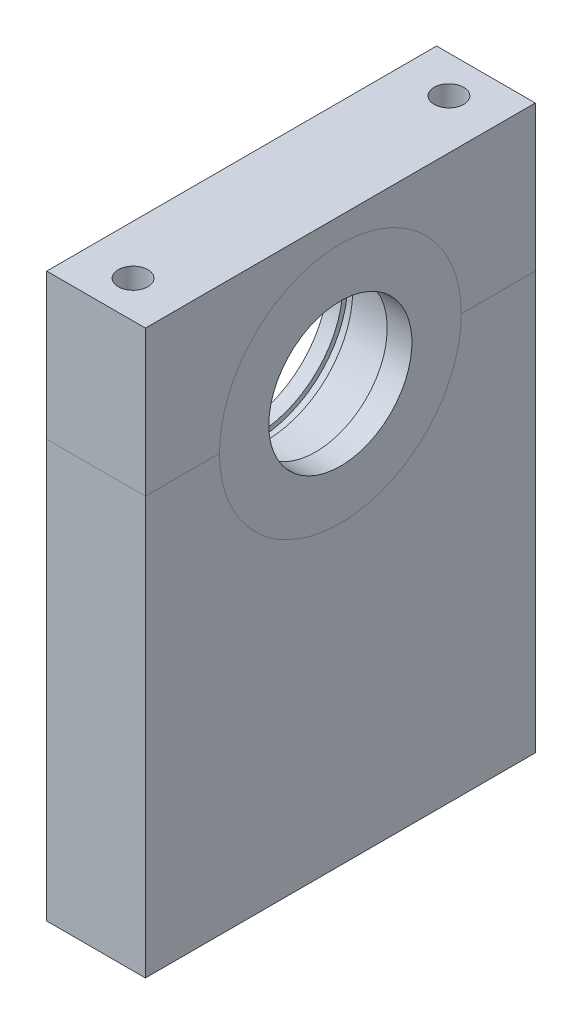
SolidWorks part; units mm, degrees
ref_plane "Front Plane" through (0, 0, 0) normal (0, 0, 1) x (1, 0, 0)
ref_plane "Top Plane" through (0, 0, 0) normal (0, 1, 0) x (1, 0, 0)
ref_plane "Right Plane" through (0, 0, 0) normal (1, 0, 0) x (0, 0, -1)
sketch "Sketch1" plane through (0, 0, 0) normal (0, 0, 1) x (1, 0, 0)
  line L0 (-44.079, 28.0482) -> (-34.079, 28.0482)
  line L1 (-34.079, 28.0482) -> (-34.079, 25.0482)
  line L2 (-34.079, 25.0482) -> (-29.079, 25.0482)
  line L3 (-29.079, 25.0482) -> (-29.079, 35.0482)
  line L4 (-29.079, 35.0482) -> (-49.079, 35.0482)
  line L5 (-49.079, 35.0482) -> (-49.079, 28.0482)
  line L6 (-49.079, 28.0482) -> (-46.079, 28.0482)
  line L7 (-46.079, 28.0482) -> (-46.079, 29.0482)
  line L8 (-46.079, 29.0482) -> (-44.079, 29.0482)
  line L9 (-44.079, 29.0482) -> (-44.079, 28.0482)
  line L10 (-85.0679, 10.5482) -> (6.0387, 10.5482) construction
  dimension "D1" = 24.5
  dimension "D2" = 20
  dimension "D3" = 17.5
  dimension "D4" = 2
  dimension "D5" = 10
  dimension "D6" = 3
  dimension "D7" = 1
  dimension "D8" = 3
revolve "Revolve1" add sketch "Sketch1" angle 360 about L10
sketch "Sketch2" plane through (-49.079, 0, 0) normal (-1, 0, 0) x (0, 0, 1)
  line L0 (-24.5, 10.5482) -> (-39.5, 10.5482)
  line L1 (-39.5, -18.9518) -> (39.5, -18.9518)
  line L2 (-39.5, -18.9518) -> (-39.5, 40.0482)
  line L3 (-39.5, 40.0482) -> (39.5, 40.0482)
  line L4 (39.5, -18.9518) -> (39.5, 40.0482)
  line L5 (0, 40.0482) -> (0, -18.9518) construction
  line L6 (-39.5, 10.5482) -> (39.5, 10.5482) construction
  line L7 (24.5, 10.5482) -> (39.5, 10.5482)
  line L8 (-34.5, 40.0482) -> (-34.5, -18.9518) construction
  line L9 (-29.5, 40.0482) -> (-29.5, -18.9518) construction
  line L10 (29.5, 40.0482) -> (29.5, -18.9518) construction
  line L11 (34.5, 40.0482) -> (34.5, -18.9518) construction
  circle A0 centre (0, 10.5482) radius 24.5 construction
  circle A1 centre (0, 10.5482) radius 24.5 construction
  point P0 (0, 10.5482)
  point P7 (0, 35.0482)
  point P9 (0, -13.9518)
  point P10 (24.5, 10.5482)
  point P11 (-24.5, 10.5482)
  circle M9 centre (0, 10.5482) radius 24.5
  dimension "D1" = 49
  dimension "D2" = 5
  dimension "D3" = 5
  dimension "D4" = 15
  dimension "D5" = 15
  dimension "D6" = 5
  dimension "D7" = 5
  dimension "D8" = 5
extrude "Boss-Extrude2" add sketch "Sketch2" against normal up to surface (20 mm away) separate body contours L7 L4 L3 L2 L0 M9 region at (-49.079, 11.3915, -32) up to face at (-29.079, 10.5482, 24.5)
extrude "Boss-Extrude3" add sketch "Sketch2<3>" against normal up to surface (20 mm away) separate body contours L7 L0 L2 L1 L4 M9 region at (-49.079, -14.7951, 0) up to face at (-29.079, 10.5482, 24.5)
sketch "Sketch2<3>" plane through (-49.079, 0, 0) normal (-1, 0, 0) x (0, 0, 1) same geometry as "Sketch2"
sketch "Sketch3" plane through (0, 40.0482, 0) normal (0, 1, 0) x (1, 0, 0)
  line L0 (-39.079, -39.5) -> (-39.079, 39.5) construction
  line L1 (-29.079, -39.5) -> (-49.079, -39.5) construction
  line L2 (-29.079, 39.5) -> (-49.079, 39.5) construction
  circle A0 centre (-39.079, 32) radius 3
  circle A1 centre (-39.079, -32) radius 3
  dimension "D1" = 7.5
  dimension "D3" = 6
  dimension "D4" = 6
  dimension "D2" = 7.5
extrude "Cut-Extrude1" cut sketch "Sketch3" against normal up to surface (59 mm away) up to face at (-39.079, -18.9518, 0)
sketch "Sketch4" plane through (0, -18.9518, 0) normal (0, -1, 0) x (1, 0, 0)
  line L0 (-29.079, 39.5) -> (-29.079, -39.5) construction
  line L1 (-49.079, 39.5) -> (-29.079, 39.5)
  line L2 (-49.079, 39.5) -> (-49.079, -39.5)
  line L3 (-49.079, -39.5) -> (-29.079, -39.5)
  line L4 (-29.079, 39.5) -> (-29.079, -39.5)
  circle A0 centre (-39.079, 32) radius 3
  circle A1 centre (-39.079, -32) radius 3
extrude "Boss-Extrude5" add sketch "Sketch4" along normal blind 55.05
